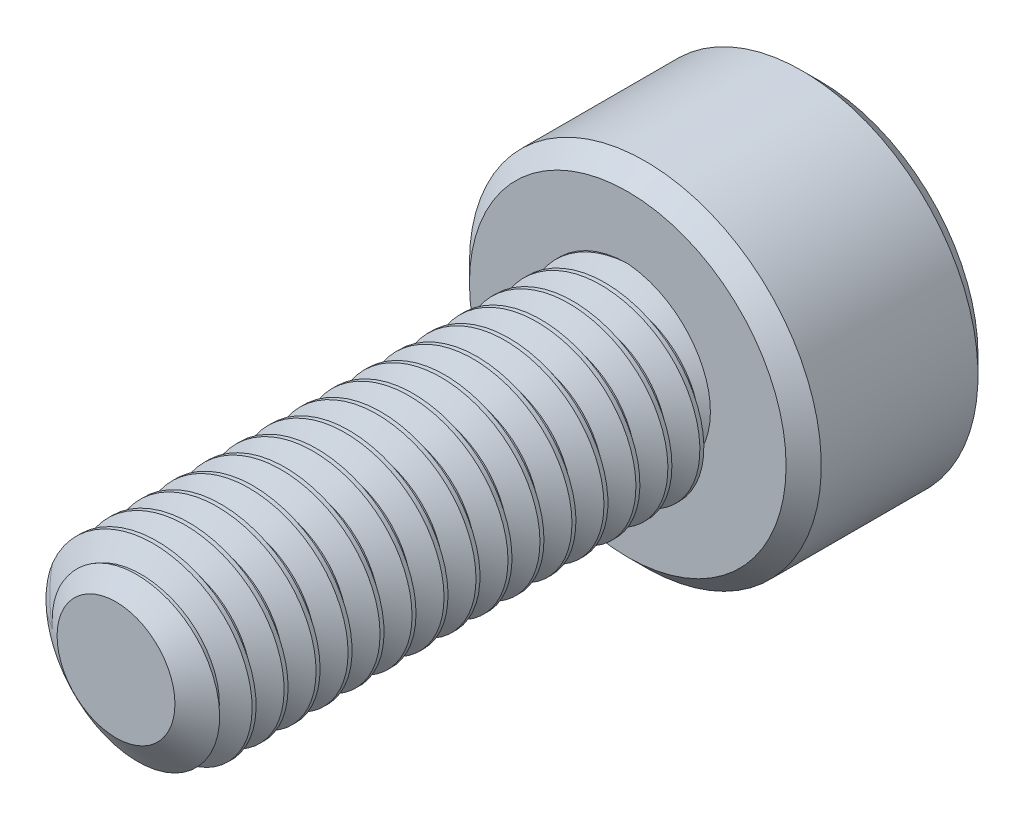
SolidWorks part; units mm, degrees
other "DetailItem1"
ref_plane "Front Plane" through (0, 0, 0) normal (0, 0, 1) x (1, 0, 0)
ref_plane "Top Plane" through (0, 0, 0) normal (0, 1, 0) x (1, 0, 0)
ref_plane "Right Plane" through (0, 0, 0) normal (1, 0, 0) x (0, 0, -1)
sketch "Sketch1" plane through (0, 0, 0) normal (0, 0, 1) x (1, 0, 0)
  circle A0 centre (0, 0) radius 1.5
  dimension "OD" = 3
extrude "Extrude1" add sketch "Sketch1" against normal blind 8
sketch "Sketch2" plane through (0, 0, 0) normal (0, 0, 1) x (1, 0, 0)
  circle A0 centre (0, 0) radius 1.5 construction
  circle A1 centre (0, 0) radius 1.5
curve "Helix/Spiral1" pitch 0.5 height 8.5 radius 1.5 centre (0, 0, 0) axis (0, 0, -1) start towards (0, 1, 0) parameters "pitch"=0.5
sketch "Sketch3" plane through (0, 0, 0) normal (1, 0, 0) x (0, 0, -1)
  line L0 (-0.4375, 1.5) -> (-0.25, 1.1752)
  line L1 (-0.25, 1.1752) -> (-0.1875, 1.1752)
  line L2 (-0.1875, 1.1752) -> (0, 1.5)
  line L3 (-0.4375, 1.5) -> (0, 1.5)
  line L4 (-0.2187, 1.5) -> (-0.2188, 1.1752) construction
  line L5 (-0.3438, 1.3376) -> (-0.0938, 1.3376) construction
  line L6 (0, 1.5) -> (0, -1.5) construction
  dimension "D1" = 0.0625
  dimension "D2" = 0.25
  dimension "D3" = 60
sweep "Cut-Sweep1" cut profiles "Sketch3" path "Helix/Spiral1" align with end faces yes
sketch "Sketch4" plane through (0, 0, 0) normal (1, 0, 0) x (0, 0, -1)
  line L0 (0.4053, 1.5) -> (0, 0.9212)
  line L1 (0, 0.9212) -> (0, 1.5)
  line L2 (0.4053, 1.5) -> (0, 1.5)
  line L3 (-0.4375, 1.5) -> (0, 1.5) construction
  line L4 (0, 0) -> (7.0209, 0) construction
  dimension "D1" = 55
  dimension "D2" = 0.254
revolve "Cut-Revolve1" cut sketch "Sketch4" angle 360 about L4
sketch "Sketch6" plane through (0, 0, -8) normal (0, 0, -1) x (-1, 0, 0)
  circle A0 centre (0, 0) radius 2.75
  dimension "head dia" = 5.5
extrude "Extrude2" add sketch "Sketch6" along normal blind 3
sketch "Sketch7" plane through (0, 0, -11) normal (0, 0, -1) x (-1, 0, 0)
  line L1 (0, 1.4434) -> (-1.25, 0.7217)
  line L2 (-1.25, 0.7217) -> (-1.25, -0.7217)
  line L3 (-1.25, -0.7217) -> (0, -1.4434)
  line L4 (0, -1.4434) -> (1.25, -0.7217)
  line L5 (1.25, -0.7217) -> (1.25, 0.7217)
  line L6 (1.25, 0.7217) -> (0, 1.4434)
  circle A0 centre (0, 0) radius 1.25 construction
  dimension "hex dia" = 2.5
extrude "Cut-Extrude1" cut sketch "Sketch7" against normal blind 1.875
sketch "Sketch8" plane through (0, 0, -11) normal (0, 0, -1) x (-1, 0, 0)
  circle A0 centre (0, 0) radius 1.4434
extrude "Cut-Extrude2" cut sketch "Sketch8" against normal through all draft 45
chamfer "Chamfer1" distance 0.275 angle 45 2 edges at (-2.75, 0, -11) (-2.75, 0, -8)
sketch "Sketch10" plane through (0, 0, -8) normal (0, 0, 1) x (1, 0, 0)
  circle A1 centre (0, 0) radius 1.5
  circle A2 centre (0, 0) radius 1.5
  dimension "D1" = 0
ref_plane "Plane1" through (0, 0, 0) normal (0, 0, 1) x (1, 0, 0)
extrude "partial thread" [suppressed] add sketch "Sketch10" along normal up to surface (4 mm away) separate body up to plane "Plane1"
chamfer "Chamfer2" [suppressed] distance 0.06 angle 45
combine bodies "Combine1" [suppressed] operation type add bodies to combine 107 108
sketch "Sketch9" plane through (0, 0, 0) normal (1, 0, 0) x (0, 0, -1)
  line L0 (0, 1.5) -> (0, -1.5) construction
  line L1 (1.25, 1.5) -> (1.25, -1.5) construction
  dimension "D1" = 1.25
equation "\"D3@Helix/Spiral1\" = \"screw length@Extrude1\"+\"pitch@Helix/Spiral1\""
equation "\"D1@Sketch3\" = \"pitch@Helix/Spiral1\"*.125"
equation "\"D2@Sketch3\" = \"pitch@Helix/Spiral1\"*.5"
equation "\"D1@Cut-Extrude1\" = \"hex dia@Sketch7\"*.75"
equation "\"D1@Chamfer1\" = \"head dia@Sketch6\"*.05"
equation "\"D1@Sketch9\" = \"pitch@Helix/Spiral1\"*2.5"
equation "\"D1@Chamfer2\"=\"OD@Sketch1\"*.02"
